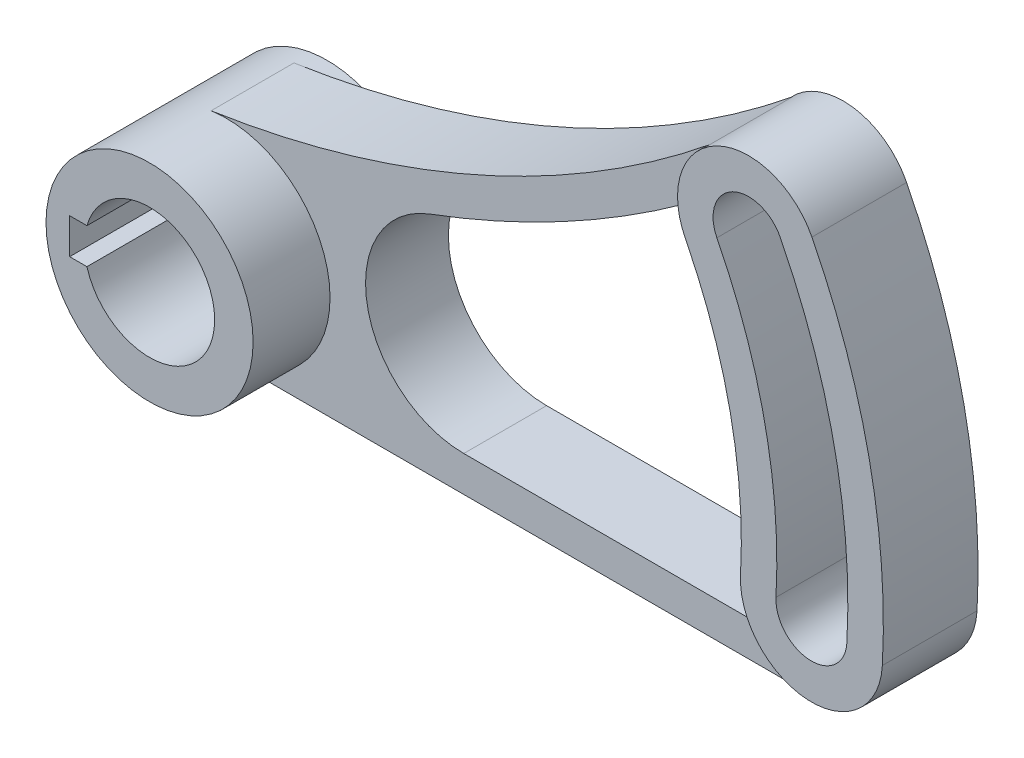
SolidWorks part; units mm, degrees
ref_plane "Front Plane" through (0, 0, 0) normal (0, 0, 1) x (1, 0, 0)
ref_plane "Top Plane" through (0, 0, 0) normal (0, 1, 0) x (1, 0, 0)
ref_plane "Right Plane" through (0, 0, 0) normal (1, 0, 0) x (0, 0, -1)
sketch "Sketch1" plane through (0, 0, 0) normal (0, 0, 1) x (1, 0, 0)
  line L0 (0, 0) -> (11, 0) construction
  line L1 (-10.583, 3) -> (-13.5, 3)
  line L2 (-10.583, -3) -> (-13.5, -3)
  line L3 (-13.5, 3) -> (-13.5, -3)
  arc A0 (-10.583, -3) -> (-10.583, 3) centre (0, 0) ccw
  circle A1 centre (0, 0) radius 17.5
  point P9 (0, 0)
  point P10 (-14.9517, -4.5)
  dimension "D1" = 35
  dimension "D2" = 22
  dimension "D3" = 6
  dimension "D4" = 3
  dimension "D5" = 24.5
  dimension "D6" = 3
extrude "Boss-Extrude1" add sketch "Sketch1" along normal blind 30
ref_plane "Plane1" through (0, 0, 10) normal (0, 0, 1) x (1, 0, 0)
sketch "Sketch2" plane through (0, 0, 10) normal (0, 0, 1) x (1, 0, 0)
  line L0 (0, -17.5) -> (99.8486, -17.5)
  line L1 (0, 0) -> (99.8486, -5.5) construction
  line L2 (0, 0) -> (89.2215, 45.1612) construction
  line L3 (89.4563, -11.5) -> (40.0967, -11.5)
  line L4 (17.5, 10.6103) -> (17.5, -9.1503) construction
  line L5 (23.5, 14.8663) -> (23.5, -5.644) construction
  circle A0 centre (0, 0) radius 17.5 construction
  circle A1 centre (0, 0) radius 100 construction
  arc A2 (87.8668, -4.84) -> (111.8305, -6.16) centre (99.8486, -5.5) ccw
  arc A3 (93.8577, -5.17) -> (105.8396, -5.83) centre (99.8486, -5.5) ccw
  arc A4 (99.928, 50.5805) -> (78.5149, 39.7418) centre (89.2215, 45.1612) ccw
  arc A5 (94.5747, 47.8708) -> (83.8682, 42.4515) centre (89.2215, 45.1612) ccw
  arc A6 (99.928, 50.5805) -> (111.8305, -6.16) centre (0, 0) cw
  arc A7 (78.5149, 39.7418) -> (87.8668, -4.84) centre (0, 0) cw
  arc A8 (93.8577, -5.17) -> (83.8682, 42.4515) centre (0, 0) ccw
  arc A9 (94.5747, 47.8708) -> (105.8396, -5.83) centre (0, 0) cw
  arc A10 (-2.6016, 17.3055) -> (81.6596, 54.4788) centre (-28.6175, 190.3609) ccw
  arc A11 (77.3229, 43.6039) -> (34.3252, 20.6576) centre (-28.6175, 190.3609) cw
  arc A12 (40.0967, -11.5) -> (34.3252, 20.6576) centre (40.0967, 5.0967) cw
  arc A13 (-2.6016, 17.3055) -> (0, -17.5) centre (0, 0) cw
  dimension "D1" = 200
  dimension "D2" = 24
  dimension "D3" = 6
  dimension "D5" = 24
  dimension "D6" = 12
  dimension "D7" = 175
  dimension "D9" = 6
  dimension "D4" = 30
  dimension "D8" = 6
  dimension "D10" = 6
extrude "Boss-Extrude2" add sketch "Sketch2" along normal mid plane 14 contours A10 A13 L0 A2 L3 A12 A11 A4 region at (18.6999, 1.3978, 10)
extrude "Boss-Extrude3" add sketch "Sketch2<3>" along normal mid plane 16 contours A4 A7 A2 A6 A5 A9 A3 A8 region at (94.2605, -15.179, 10)
sketch "Sketch2<3>" plane through (0, 0, 10) normal (0, 0, 1) x (1, 0, 0) same geometry as "Sketch2"
